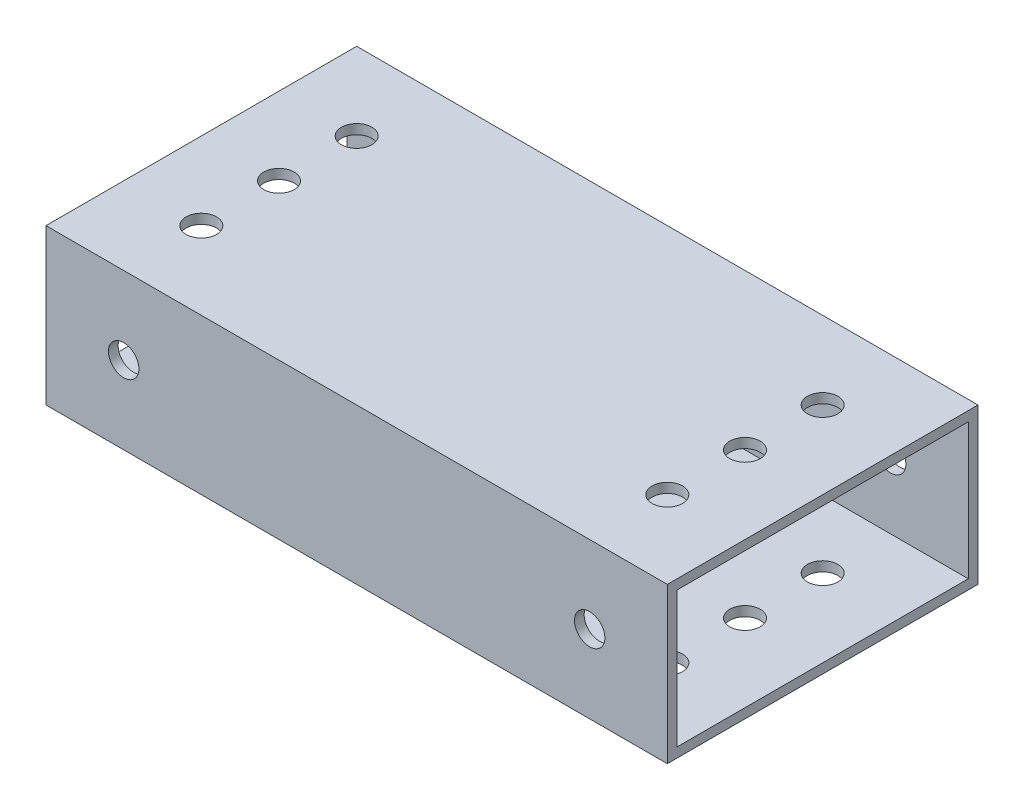
SolidWorks part; units mm, degrees
material "6061-T6 (SS)"
ref_plane "Front Plane" through (0, 0, 0) normal (0, 0, 1) x (1, 0, 0)
ref_plane "Top Plane" through (0, 0, 0) normal (0, 1, 0) x (1, 0, 0)
ref_plane "Right Plane" through (0, 0, 0) normal (1, 0, 0) x (0, 0, -1)
sketch "Sketch1" plane through (0, 0, 0) normal (1, 0, 0) x (0, 0, -1)
  line L1 (0, 0) -> (50.8, 0)
  line L2 (0, 0) -> (0, 25.4)
  line L3 (0, 25.4) -> (50.8, 25.4)
  line L4 (50.8, 0) -> (50.8, 25.4)
  dimension "D1" = 25.4
  dimension "D2" = 50.8
extrude "Boss-Extrude1" add sketch "Sketch1" along normal mid plane 101.6
shell "Shell1" thickness 1.5875 removed face at (-50.8, 12.7, -25.4) removed face at (50.8, 12.7, -25.4)
sketch "Sketch2" plane through (0, 25.4, 0) normal (0, 1, 0) x (1, 0, 0)
  line L0 (-38.1, 50.8) -> (-38.1, 0) construction
  line L1 (50.8, 50.8) -> (-50.8, 50.8) construction
  line L2 (50.8, 0) -> (-50.8, 0) construction
  line L3 (-50.8, 50.8) -> (-50.8, 0) construction
  circle A0 centre (-38.1, 25.4) radius 2.4892
  circle A1 centre (-38.1, 12.7) radius 2.4892
  circle A2 centre (-38.1, 38.1) radius 2.4892
  dimension "D1" = 4.9784
  dimension "D2" = 12.7
  dimension "D3" = 12.7
  dimension "D4" = 12.7
extrude "Cut-Extrude1" cut sketch "Sketch2" against normal through all
sketch "Sketch3" plane through (0, 0, 0) normal (0, 0, 1) x (1, 0, 0)
  line L0 (50.8, 25.4) -> (-50.8, 25.4) construction
  line L1 (-50.8, 25.4) -> (-50.8, 0) construction
  circle A0 centre (-38.1, 12.7) radius 2.4892
  point P8 (-4.8888, 12.7)
  point P9 (-4.9098, 11.5194)
  dimension "D3" = 4.9784
  dimension "D1" = 12.7
  dimension "D2" = 12.7
extrude "Cut-Extrude2" cut sketch "Sketch3" against normal through all
mirror "Mirror1" about plane through (0, 0, 0) normal (1, 0, 0) of "Cut-Extrude2", "Cut-Extrude1"
